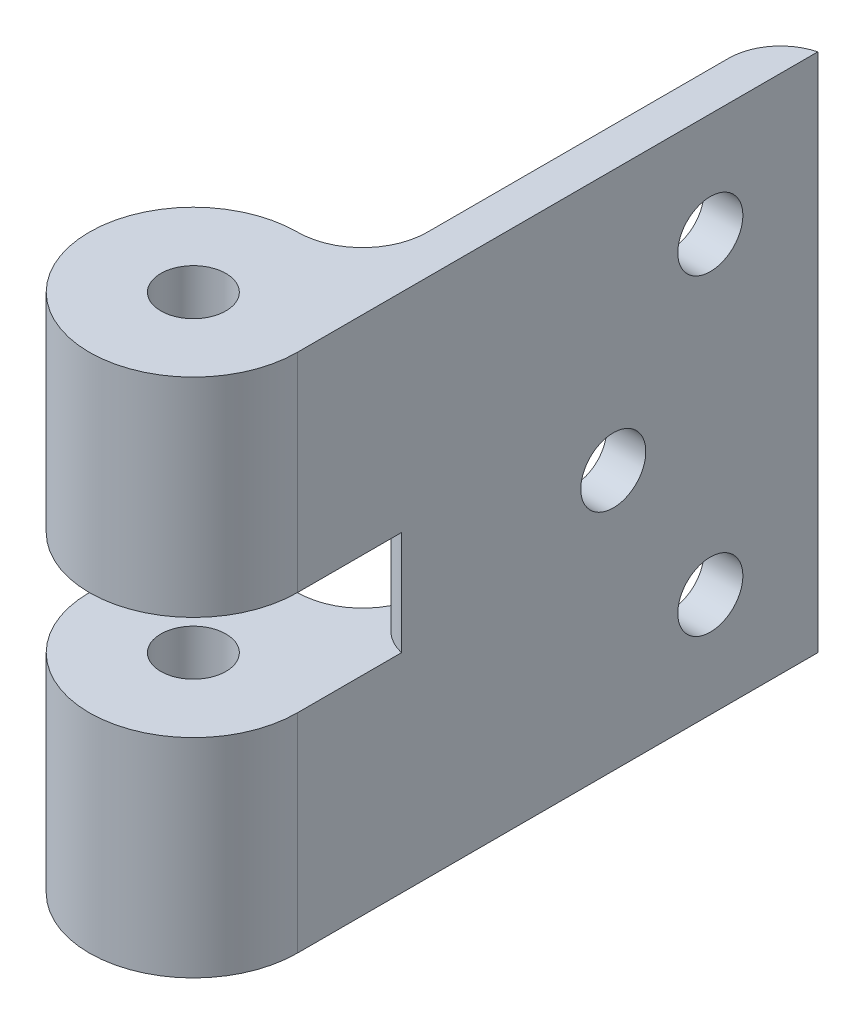
SolidWorks part; units mm, degrees
ref_plane "Front Plane" through (0, 0, 0) normal (0, 0, 1) x (1, 0, 0)
ref_plane "Top Plane" through (0, 0, 0) normal (0, 1, 0) x (1, 0, 0)
ref_plane "Right Plane" through (0, 0, 0) normal (1, 0, 0) x (0, 0, -1)
sketch "Sketch1" plane through (0, 0, 0) normal (0, 1, 0) x (1, 0, 0)
  line L0 (4, 0) -> (4, 20)
  line L1 (2.5, 6.5) -> (2.5, 15.12)
  line L5 (2.5, 15.12) -> (2.5, 20)
  line L6 (2.5, 20) -> (4, 20)
  circle A0 centre (0, 0) radius 1.25
  arc A1 (0, 4) -> (4, 0) centre (0, 0) ccw
  arc A2 (2.5, 6.5) -> (0, 4) centre (0, 6.5) cw
  dimension "D1" = 2.5
  dimension "D2" = 8
  dimension "D4" = 2.5
  dimension "D3" = 20
extrude "Boss-Extrude1" add sketch "Sketch1" along normal blind 20
sketch "Sketch2" plane through (2.5, 0, 0) normal (-1, 0, 0) x (0, 0, 1)
  line L0 (-6.5, 20) -> (-6.5, 0) construction
  circle A0 centre (-12.1392, 10) radius 1.25
  circle A1 centre (-15.8687, 4) radius 1.25
  circle A2 centre (-15.8687, 16) radius 1.25
  point P11 (-6.5, 10)
  dimension "D1" = 2.5
extrude "Cut-Extrude1" cut sketch "Sketch2" against normal through all both and the other way through all
sketch "Sketch3" plane through (0, 0, 0) normal (1, 0, 0) x (0, 0, -1)
  line L0 (-4, 20) -> (-4, 0) construction
  line L1 (4, 12) -> (-4, 12)
  line L2 (4, 12) -> (4, 8)
  line L3 (4, 8) -> (-4, 8)
  line L4 (-4, 12) -> (-4, 8)
  line L5 (4, 12) -> (-4, 8) construction
  line L6 (4, 8) -> (-4, 12) construction
  line L7 (4, 20) -> (-4, 20) construction
  line L8 (-4, 0) -> (4, 0) construction
  line L9 (4, 20) -> (4, 0) construction
  point P0 (0, 10)
  dimension "D1" = 8
  dimension "D2" = 8
extrude "Cut-Extrude2" cut sketch "Sketch3" against normal through all both and the other way through all
fillet "Fillet1" radius 2 2 edges at (2.5, 10, -20) (0, 10, -4)
